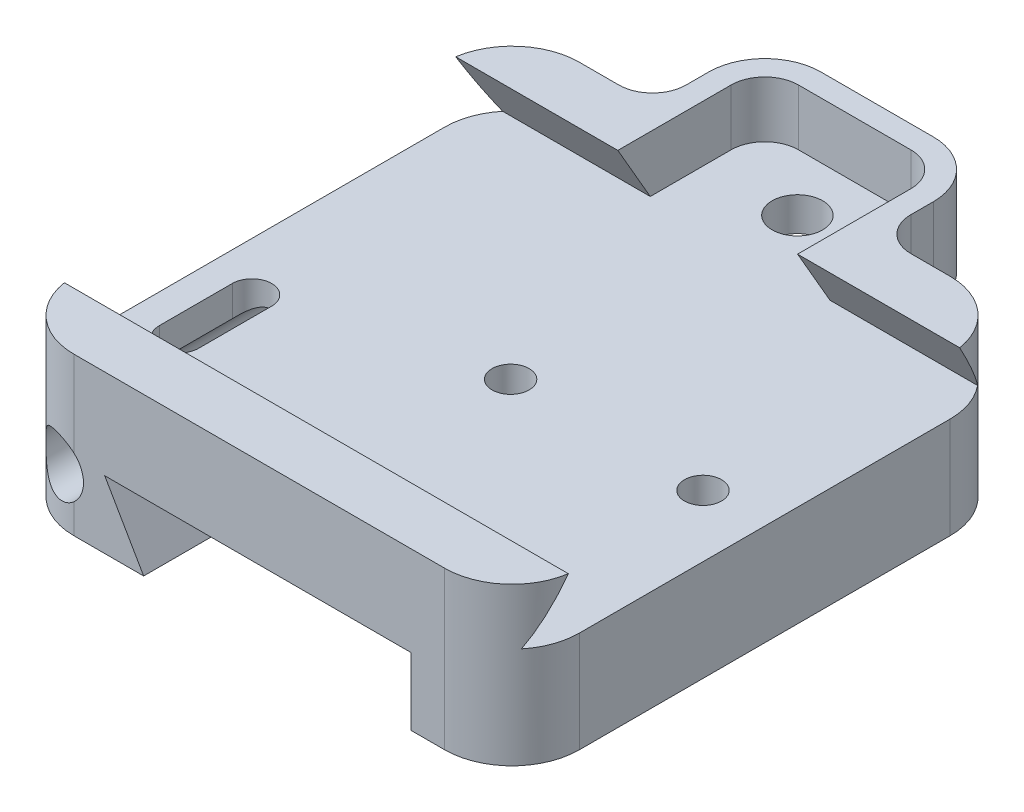
SolidWorks part; units mm, degrees
material "Сплав 2024"
ref_plane "Спереди" through (0, 0, 0) normal (0, 0, 1) x (1, 0, 0)
ref_plane "Сверху" through (0, 0, 0) normal (0, 1, 0) x (1, 0, 0)
ref_plane "Справа" through (0, 0, 0) normal (1, 0, 0) x (0, 0, -1)
sketch "Эскиз1" plane through (0, 0, 0) normal (0, 1, 0) x (1, 0, 0)
  line L1 (0, 0) -> (45, 0)
  line L2 (0, 0) -> (0, 45)
  line L3 (0, 45) -> (45, 45)
  line L4 (45, 0) -> (45, 45)
  dimension "D1" = 45
  dimension "D2" = 45
extrude "Бобышка-Вытянуть1" add sketch "Эскиз1" along normal blind 16
sketch "Эскиз2" plane through (0, 0, 0) normal (0, 0, 1) x (1, 0, 0)
  line L0 (22.5, 0) -> (22.5, 5.4603) construction
  line L1 (0, 0) -> (45, 0) construction
  line L2 (8.7453, 8) -> (36.2547, 8)
  line L3 (13.3641, 0) -> (8.7453, 8)
  line L4 (36.2547, 8) -> (31.6359, 0)
  line L5 (31.6359, 0) -> (13.3641, 0)
  line L6 (9.9, 8) -> (9.9, 6) construction
  line L7 (35.1, 8) -> (35.1, 6) construction
  dimension "D1" = 60
  dimension "D2" = 60
  dimension "D3" = 8
  dimension "D4" = 2
  dimension "D5" = 2
  dimension "D6" = 25.2
  dimension "D7" = 12.6
extrude "Вырез-Вытянуть1" cut sketch "Эскиз2" against normal through all
sketch "Эскиз3" plane through (0, 0, 0) normal (0, -1, 0) x (1, 0, 0)
  line L0 (45, -22.5) -> (31.6359, -22.5) construction
  line L1 (45, 0) -> (45, -45) construction
  line L2 (31.6359, -45) -> (31.6359, 0) construction
  line L3 (45, -45) -> (31.6359, -45) construction
  line L4 (31.6359, 0) -> (45, 0)
  line L5 (31.6359, 0) -> (31.6359, -45)
  line L6 (31.6359, -45) -> (45, -45)
  line L7 (45, 0) -> (45, -45)
  line L8 (31.6359, 0) -> (45, -45) construction
  line L9 (31.6359, -45) -> (45, 0) construction
  point P6 (38.3179, -22.5)
extrude "Вырез-Вытянуть2" cut sketch "Эскиз3" against normal up to surface (8 mm away) up to face at (22.5, 8, -22.5)
sketch "Эскиз4" plane through (45, 0, 0) normal (1, 0, 0) x (0, 0, -1)
  line L0 (5.0821, 16) -> (2.1953, 11)
  line L1 (0, 16) -> (45, 16) construction
  line L2 (2.1953, 11) -> (42.8047, 11)
  line L3 (42.8047, 11) -> (39.9179, 16)
  line L4 (39.9179, 16) -> (5.0821, 16)
  line L5 (22.5, 16) -> (22.5, 13.5478) construction
  line L6 (3.35, 13) -> (3.35, 11) construction
  line L7 (41.65, 13) -> (41.65, 11) construction
  dimension "D1" = 5
  dimension "D2" = 60
  dimension "D3" = 60
  dimension "D4" = 2
  dimension "D5" = 38.3
  dimension "D6" = 19.15
extrude "Вырез-Вытянуть3" cut sketch "Эскиз4" against normal up to next
fillet "Скругление1" radius 6 4 edges at (0, 8, -45) (45, 12, -45) (45, 12, 0) (0, 8, 0)
sketch "-2mm" plane through (0, 0, 0) normal (0, -1, 0) x (1, 0, 0)
  line L1 (-3.5072, 3.737) -> (47.0368, 3.737)
  line L2 (-3.5072, 3.737) -> (-3.5072, -49.0127)
  line L3 (-3.5072, -49.0127) -> (47.0368, -49.0127)
  line L4 (47.0368, 3.737) -> (47.0368, -49.0127)
  line L5 (-3.5072, 3.737) -> (47.0368, -49.0127) construction
  line L6 (-3.5072, -49.0127) -> (47.0368, 3.737) construction
  point P0 (21.7648, -22.6378)
extrude "Вырез-Вытянуть4" cut sketch "-2mm" against normal blind 2
sketch "Эскиз6" plane through (0, 0, 0) normal (0, 0, 1) x (1, 0, 0)
  line L0 (12.2094, 2) -> (6, 2) construction
  circle A0 centre (4.3524, 6.5) radius 2.5
  dimension "D1" = 5
  dimension "D2" = 4.5
sketch "Эскиз7" plane through (0, 8, 0) normal (0, -1, 0) x (1, 0, 0)
  line L2 (45, -39) -> (45, -6) construction
  line L3 (43, -39) -> (43, -6)
  line L4 (43, -39) -> (43, -6)
  line L5 (45, -39) -> (45, -6)
  line L8 (39, 0) -> (8.7453, 0) construction
  line L9 (39, -2) -> (36, -2)
  line L10 (39, -45) -> (36, -45)
  line L11 (39, 0) -> (36, 0)
  line L12 (36, -2) -> (36, 0)
  line L14 (39, -43) -> (36, -43)
  line L15 (36, -45) -> (36, -43)
  arc A2 (45, -6) -> (39, 0) centre (39, -6) ccw construction
  arc A3 (39, -45) -> (45, -39) centre (39, -39) ccw construction
  arc A4 (39, -43) -> (43, -39) centre (39, -39) ccw
  arc A5 (43, -6) -> (39, -2) centre (39, -6) ccw
  arc A6 (39, -43) -> (43, -39) centre (39, -39) ccw
  arc A7 (43, -6) -> (39, -2) centre (39, -6) ccw
  arc A8 (45, -6) -> (39, 0) centre (39, -6) ccw
  arc A9 (39, -45) -> (45, -39) centre (39, -39) ccw
  dimension "D1" = 2
  dimension "D2" = 3
  dimension "D3" = 3
extrude "Бобышка-Вытянуть2" add sketch "Эскиз7" along normal blind 6
extrude "Вырез-Вытянуть5" cut sketch "Эскиз6" against normal blind 30
sketch "Эскиз8" plane through (0, 8, 0) normal (0, -1, 0) x (1, 0, 0)
  line L0 (36, -2) -> (39, -2) construction
  line L1 (43, -6) -> (43, -39) construction
  line L2 (39, -43) -> (36, -43) construction
  line L3 (36, -2) -> (39, -2)
  line L4 (43, -6) -> (43, -39)
  line L5 (39, -43) -> (36, -43)
  line L6 (36, -2) -> (36, -43)
  arc A0 (43, -6) -> (39, -2) centre (39, -6) ccw construction
  arc A1 (39, -43) -> (43, -39) centre (39, -39) ccw construction
  arc A2 (43, -6) -> (39, -2) centre (39, -6) ccw
  arc A3 (39, -43) -> (43, -39) centre (39, -39) ccw
extrude "Бобышка-Вытянуть3" add sketch "Эскиз8" along normal blind 2
sketch "Эскиз9" plane through (0, 16, 0) normal (0, 1, 0) x (1, 0, 0)
  line L0 (22.5, 45) -> (22.5, 54.4822) construction
  line L1 (39, 45) -> (6, 45) construction
  line L3 (12.5, 45) -> (32.5, 45)
  line L4 (12.5, 45) -> (12.5, 55)
  line L5 (12.5, 55) -> (32.5, 55)
  line L6 (32.5, 45) -> (32.5, 55)
  line L7 (12.5, 45) -> (32.5, 55) construction
  line L8 (12.5, 55) -> (32.5, 45) construction
  point P4 (22.5, 50)
  dimension "D1" = 10
  dimension "D2" = 20
extrude "Бобышка-Вытянуть4" add sketch "Эскиз9" against normal up to surface (8 mm away) up to face at (22.3726, 8, -22.5)
fillet "Скругление2" radius 5 2 edges at (12.5, 12, -55) (32.5, 12, -55)
sketch "Эскиз10" plane through (0, 16, 0) normal (0, 1, 0) x (1, 0, 0)
  line L1 (14.5, 50) -> (14.5, 39.9179)
  line L2 (27.5, 53) -> (17.5, 53)
  line L3 (27.5, 53) -> (17.5, 53)
  line L4 (0.0706, 39.9179) -> (44.9294, 39.9179) construction
  line L5 (14.5, 39.9179) -> (30.5, 39.9179)
  line L6 (30.5, 39.9179) -> (30.5, 50)
  arc A4 (30.5, 50) -> (27.5, 53) centre (27.5, 50) ccw
  arc A5 (17.5, 53) -> (14.5, 50) centre (17.5, 50) ccw
  arc A6 (30.5, 50) -> (27.5, 53) centre (27.5, 50) ccw
  arc A7 (17.5, 53) -> (14.5, 50) centre (17.5, 50) ccw
  dimension "D1" = 2
extrude "Вырез-Вытянуть6" cut sketch "Эскиз10" against normal up to surface (5 mm away) up to face at (22.5, 11, -22.5)
fillet "Скругление3" radius 3 2 edges at (32.5, 12, -45) (12.5, 12, -45)
sketch "Эскиз11" plane through (0, 11, 0) normal (0, 1, 0) x (1, 0, 0)
  line L0 (14.5, 42.8047) -> (30.5, 42.8047) construction
  line L1 (22.5, 42.8047) -> (22.5, 53) construction
  line L2 (27.5, 53) -> (17.5, 53) construction
hole_wizard "Отверстие с зазором M41" positions "Эскиз13" profile "Эскиз12" hole size "M4" standard "Ansi Metric" end condition up to next
sketch "Эскиз13" plane through (0, 11, 0) normal (0, 1, 0) x (1, 0, 0)
  line L0 (22.5, 42.8047) -> (22.5, 53) construction
  point P0 (22.5, 47.9024)
sketch "Эскиз12" plane through (22.5, 11, -47.9024) normal (1, 0, 0) x (0, 0, 1)
  line L0 (0, 0) -> (0, 3)
  line L1 (0, 3) -> (2.25, 3)
  line L2 (2.25, 3) -> (2.25, 0)
  line L5 (2.25, 0) -> (0, 0)
  line L11 (0, -6.35) -> (0, 107.95) construction
  dimension "Диаметр сквозного отверстия" = 4.5
  dimension "Глубина сквозного отверстия" = 3
sketch "Эскиз14" plane through (0, 6, 0) normal (0, -1, 0) x (1, 0, 0)
  line L0 (36, -22.5) -> (43, -22.5) construction
  line L1 (36, 0) -> (36, -45) construction
  line L2 (43, -39) -> (43, -6) construction
hole_wizard "Отверстие обработанное метчиком M4x0.71" positions "Эскиз16" profile "Эскиз15" tap size "M4x0.7" standard "Ansi Metric" end condition through all
sketch "Эскиз16" plane through (0, 6, 0) normal (0, -1, 0) x (-1, 0, 0)
  line L0 (-36, 22.5) -> (-43, 22.5) construction
  point P0 (-39.5, 22.5)
sketch "Эскиз15" plane through (39.5, 6, -22.5) normal (1, 0, 0) x (0, 0, -1)
  line L0 (0, 0) -> (0, 10)
  line L1 (0, 10) -> (1.65, 10)
  line L2 (1.65, 10) -> (1.65, 0)
  line L5 (1.65, 0) -> (0, 0)
  line L11 (0, -6.35) -> (0, 107.95) construction
  dimension "Диаметр резьбы" = 3.3
  dimension "Глубина проходного сверла" = 10
ref_axis "Ось1" through (4.3524, 6.5, -30) along (0, 0, 1)
sketch "Эскиз17" plane through (0, 11, 0) normal (0, 1, 0) x (1, 0, 0)
  line L1 (4.3524, 17.5) -> (4.3524, 11) construction
  line L2 (6.1024, 17.5) -> (6.1024, 11)
  line L3 (2.6024, 17.5) -> (2.6024, 11)
  line L4 (4.3524, 30) -> (4.3524, 0) construction
  line L5 (6, 0) -> (39, 0) construction
  arc A0 (6.1024, 17.5) -> (2.6024, 17.5) centre (4.3524, 17.5) ccw
  arc A1 (2.6024, 11) -> (6.1024, 11) centre (4.3524, 11) ccw
  point P1 (4.3524, 14.25)
  dimension "D1" = 3.5
  dimension "D2" = 6.5
  dimension "D3" = 11
extrude "Вырез-Вытянуть7" cut sketch "Эскиз17" against normal up to next
sketch "Эскиз18" plane through (0, 8, 0) normal (0, -1, 0) x (1, 0, 0)
  line L0 (36, -22.5) -> (16.3635, -22.5) construction
  line L1 (36, 0) -> (36, -45) construction
  line L2 (22.3726, 0) -> (22.3726, -41.5241) construction
  line L3 (36, 0) -> (8.7453, 0) construction
hole_wizard "Отверстие обработанное метчиком M4x0.72" positions "Эскиз20" profile "Эскиз19" tap size "M4x0.7" standard "Ansi Metric" end condition up to next
sketch "Эскиз20" plane through (0, 8, 0) normal (0, -1, 0) x (-1, 0, 0)
  line L0 (-36, 22.5) -> (-16.3635, 22.5) construction
  line L1 (-22.3726, 0) -> (-22.3726, 41.5241) construction
  point P0 (-22.3726, 22.5)
sketch "Эскиз19" plane through (22.3726, 8, -22.5) normal (1, 0, 0) x (0, 0, -1)
  line L0 (0, 0) -> (0, 3)
  line L1 (0, 3) -> (1.65, 3)
  line L2 (1.65, 3) -> (1.65, 0)
  line L5 (1.65, 0) -> (0, 0)
  line L11 (0, -6.35) -> (0, 107.95) construction
  dimension "Диаметр резьбы" = 3.3
  dimension "Глубина проходного сверла" = 3
equation "\"D7@Эскиз2\"=\"D6@Эскиз2\"/2"
equation "\"D6@Эскиз4\"=\"D5@Эскиз4\"/2"
